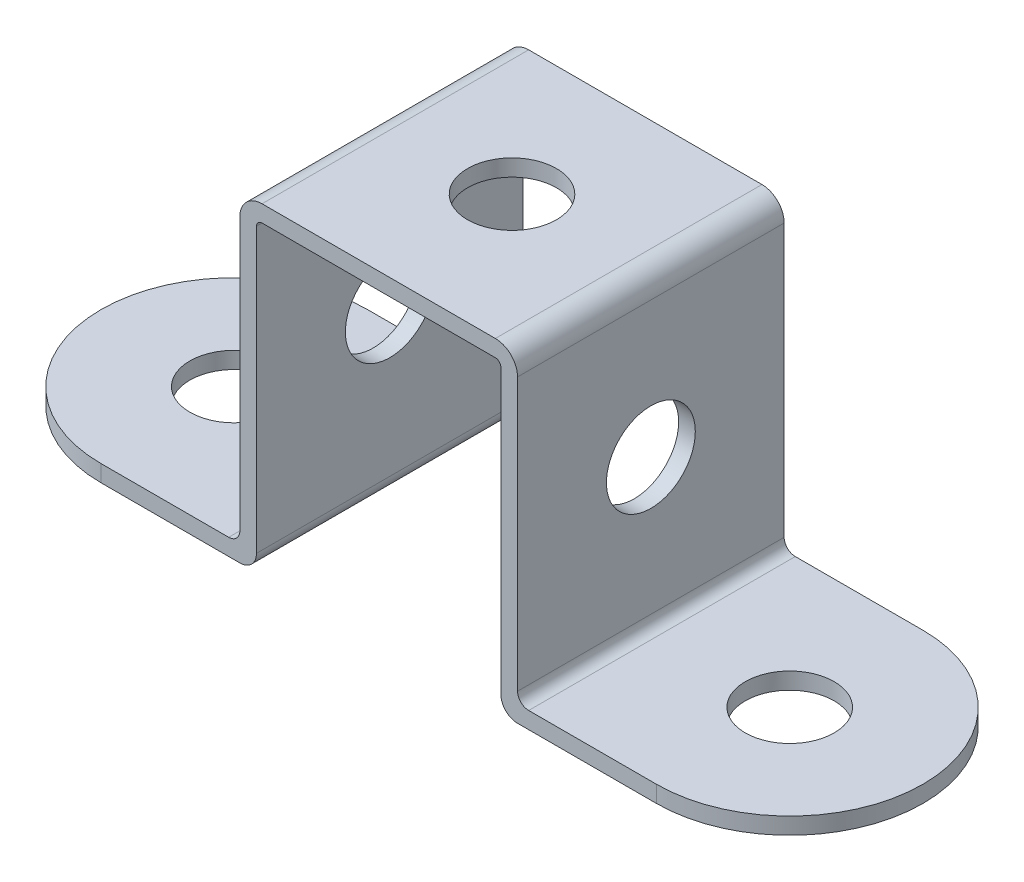
SolidWorks part; units mm, degrees
ref_plane "Piano frontale" through (0, 0, 0) normal (0, 0, 1) x (1, 0, 0)
ref_plane "Piano superiore" through (0, 0, 0) normal (0, 1, 0) x (1, 0, 0)
ref_plane "Piano destro" through (0, 0, 0) normal (1, 0, 0) x (0, 0, -1)
sketch "Schizzo1" plane through (0, 0, 0) normal (0, 0, 1) x (1, 0, 0)
  line L0 (0, 13) -> (0, 0)
  line L1 (0, 0) -> (-11, 0)
  dimension "D1" = 13
  dimension "D2" = 11
extrude "Estrusione-Sottile1" add sketch "Schizzo1" along normal mid plane 12 thin contours L0 L1 thin type one direction wall 0.75
fillet "Raccordo3" radius 6 4 edges at (-11, 0.375, 6) (-11, 0.375, -6) (-0.375, 13, -6) (-0.375, 13, 6)
sketch "Schizzo4" plane through (0, 0.75, 0) normal (0, 1, 0) x (1, 0, 0)
  circle A2 centre (-7, 0) radius 2
  dimension "D1" = 4
  dimension "D2" = 4
extrude "Taglio-Estrusione1" cut sketch "Schizzo4" against normal up to surface (0.75 mm away) up to face at (-4.6971, 0, 0)
sketch "Schizzo5" plane through (-0.75, 0, 0) normal (-1, 0, 0) x (0, 0, 1)
  line L0 (0, 9) -> (0, 3.5) construction
  line L1 (2, 9) -> (2, 3.5)
  line L2 (-2, 9) -> (-2, 3.5)
  arc A0 (2, 9) -> (-2, 9) centre (0, 9) ccw
  arc A1 (-2, 3.5) -> (2, 3.5) centre (0, 3.5) ccw
  point P3 (0, 6.25)
  point P9 (0, 11)
  point P11 (0, 1.5)
  dimension "D1" = 2
  dimension "D2" = 2
  dimension "D3" = 1.5
fillet "Raccordo1" radius 0.75 1 edges at (0, 0, 0)
fillet "Raccordo2" radius 0.5 1 edges at (-0.75, 0.75, 0)
extrude "Taglio-Estrusione2" cut sketch "Schizzo5" against normal up to surface (0.75 mm away) up to face at (0, 6.1971, 0)
sketch "Schizzo6" plane through (0, 0.75, 0) normal (0, 1, 0) x (1, 0, 0)
  line L0 (-1.25, -6) -> (-5, -6) construction
  line L1 (-1.25, 6) -> (-5, 6) construction
  line L2 (-4.125, -6) -> (-7, -6)
  line L3 (-4.125, 6) -> (-7, 6)
  line L4 (-4.125, 6) -> (-4.125, -6)
  circle A0 centre (-7, 0) radius 2 construction
  circle A1 centre (-7, 0) radius 2
  arc A2 (-7, 6) -> (-7, -6) centre (-7, 0) ccw
extrude "Estrusione-Estrusione1" add sketch "Schizzo6" against normal up to surface (0.75 mm away) up to face at (-5, 0, 0)
sketch "Schizzo7" plane through (0, 0, 0) normal (0, 0, 1) x (1, 0, 0)
  line L1 (0, 13) -> (-0.75, 13) construction
  line L2 (-0.75, 13) -> (-0.75, 7) construction
  line L3 (0, 7) -> (0, 13) construction
  line L4 (-1.25, 0.75) -> (-7, 0.75) construction
  line L6 (-7, 0) -> (-0.75, 0) construction
  line L7 (0, 0.75) -> (0, 7) construction
  line L8 (-0.75, 7) -> (-0.75, 1.25) construction
  line L9 (0, 13) -> (-0.75, 13) construction
  line L10 (-0.75, 13) -> (-0.75, 7)
  line L11 (0, 7) -> (0, 13)
  line L12 (-1.25, 0.75) -> (-4.125, 0.75)
  line L14 (-4.125, 0) -> (-0.75, 0)
  line L15 (0, 0.75) -> (0, 7)
  line L16 (-0.75, 7) -> (-0.75, 1.25)
  line L17 (-4.125, 0.75) -> (-4.125, 0)
  line L18 (-0.75, 13) -> (0, 13) construction
  line L19 (-0.75, 13) -> (-0.75, 13.5)
  line L21 (0, 13) -> (0, 13.5)
  line L23 (0.25, 14.5) -> (5.5, 14.5)
  line L25 (0.25, 13.75) -> (5.5, 13.75)
  line L26 (5.5, 14.5) -> (5.5, 13.75)
  arc A0 (-0.75, 0) -> (0, 0.75) centre (-0.75, 0.75) ccw construction
  arc A1 (-1.25, 0.75) -> (-0.75, 1.25) centre (-1.25, 1.25) ccw construction
  arc A2 (-0.75, 0) -> (0, 0.75) centre (-0.75, 0.75) ccw
  arc A3 (-1.25, 0.75) -> (-0.75, 1.25) centre (-1.25, 1.25) ccw
  arc A4 (0, 13.5) -> (0.25, 13.75) centre (0.25, 13.5) cw
  arc A5 (0.25, 14.5) -> (-0.75, 13.5) centre (0.25, 13.5) ccw
  dimension "D4" = 0.25
  dimension "D1" = 14.5
  dimension "D2" = 6.25
  dimension "D3" = 0.75
extrude "Estrusione-Estrusione3" add sketch "Schizzo7" along normal mid plane 12
mirror "Specchia2" about plane through (5.5, 14.5, 6) normal (-1, 0, 0) of "Taglio-Estrusione1", "Estrusione-Sottile1", "Raccordo3", "Raccordo1", "Raccordo2", "Estrusione-Estrusione1", "Estrusione-Estrusione3"
sketch "Schizzo8" plane through (0, 14.5, 0) normal (0, 1, 0) x (1, 0, 0)
  line L0 (10.75, -6) -> (0.25, -6) construction
  circle A0 centre (5.5, 0) radius 2
  circle A1 centre (18, 0) radius 2 construction
  circle A2 centre (18, 0) radius 2 construction
  point P5 (0, 0)
  point P8 (5.5, -6)
extrude "Taglio-Estrusione3" cut sketch "Schizzo8" against normal up to surface (0.75 mm away) up to face at (5.5, 13.75, 0)
sketch "Schizzo9" plane through (11.75, 0, 0) normal (1, 0, 0) x (0, 0, -1)
  line L0 (6, 13.5) -> (6, 1.25) construction
  line L1 (2, 0.75) -> (-2, 0.75) construction
  line L2 (2, 0.75) -> (-2, 0.75) construction
  line L3 (-2, 7.375) -> (2, 7.375) construction
  circle A0 centre (0, 7.375) radius 2
  point P2 (0, 0)
  point P5 (6, 7.375)
  point P10 (0, 0.75)
extrude "Taglio-Estrusione4" cut sketch "Schizzo9" against normal blind 19
